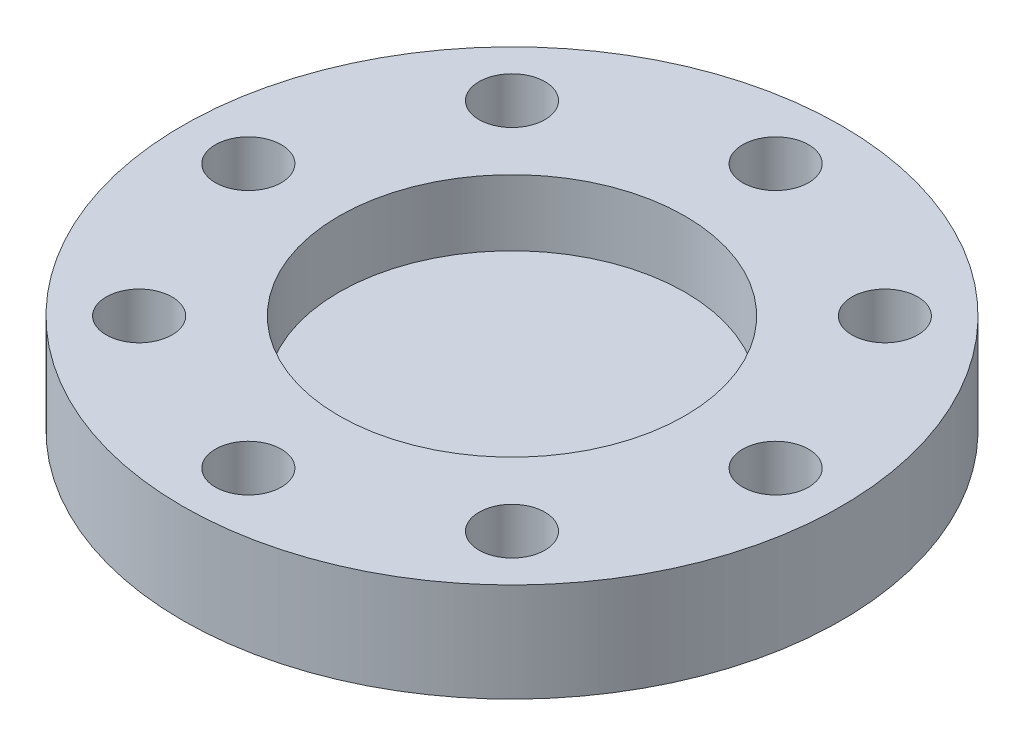
SolidWorks part; units mm, degrees
ref_plane "前视基准面" through (0, 0, 0) normal (0, 0, 1) x (1, 0, 0)
ref_plane "上视基准面" through (0, 0, 0) normal (0, 1, 0) x (1, 0, 0)
ref_plane "右视基准面" through (0, 0, 0) normal (1, 0, 0) x (0, 0, -1)
sketch "草图1" plane through (0, 0, 0) normal (0, 1, 0) x (1, 0, 0)
  circle A0 centre (0, 0) radius 10
  dimension "D1" = 20
base flange "基体-法兰1" sketch "草图1" thickness 3 reverse thickness direction no parameters "D1"=0.7366
sketch "草图6" plane through (0, 0, 0) normal (0, 1, 0) x (1, 0, 0)
  circle A0 centre (0, 0) radius 5.25
  dimension "D1" = 10.5
extrude "切除-拉伸1" cut sketch "草图6" against normal blind 2 normal cut yes
sketch "草图7" plane through (0, 0, 0) normal (0, 1, 0) x (1, 0, 0)
  circle A0 centre (0, 8) radius 1
  circle A1 centre (5.6569, 5.6569) radius 1
  circle A2 centre (8, 0) radius 1
  circle A3 centre (5.6569, -5.6569) radius 1
  circle A4 centre (0, -8) radius 1
  circle A5 centre (-5.6569, -5.6569) radius 1
  circle A6 centre (-8, 0) radius 1
  circle A7 centre (-5.6569, 5.6569) radius 1
  point P2 (0, 0)
  point P3 (0, 0)
  point P18 (0, 0)
  dimension "D1" = 2
  dimension "D3" = 16
  dimension "D2" = 8
extrude "切除-拉伸2" cut sketch "草图7" against normal through all normal cut yes
sketch "折弯-线1" plane through (0, 0, 0) normal (0, 1, 0) x (1, 0, 0)
sketch "边界框1" plane through (0, 0, 0) normal (0, 1, 0) x (1, 0, 0)
sheet metal parameters "钣金6" thickness 3 parameters "D1"=0.7366
flat pattern "平板型式6" [suppressed]
sketch "折弯-线2" plane through (0, 0, 0) normal (0, 1, 0) x (1, 0, 0)
sketch "边界框2" [suppressed] plane through (0, 0, 0) normal (0, 1, 0) x (1, 0, 0)
sheet metal parameters "钣金7" thickness 3 parameters "D1"=0.7366
flat pattern "平板型式6"
sketch "折弯-线2" plane through (0, 0, 0) normal (0, 1, 0) x (1, 0, 0)
sketch "边界框2" [suppressed] plane through (0, 0, 0) normal (0, 1, 0) x (1, 0, 0)
sheet metal parameters "钣金8" thickness 3 parameters "D1"=0.7366
flat pattern "平板型式6"
sketch "折弯-线2" plane through (0, 0, 0) normal (0, 1, 0) x (1, 0, 0)
sketch "边界框2" [suppressed] plane through (0, 0, 0) normal (0, 1, 0) x (1, 0, 0)
